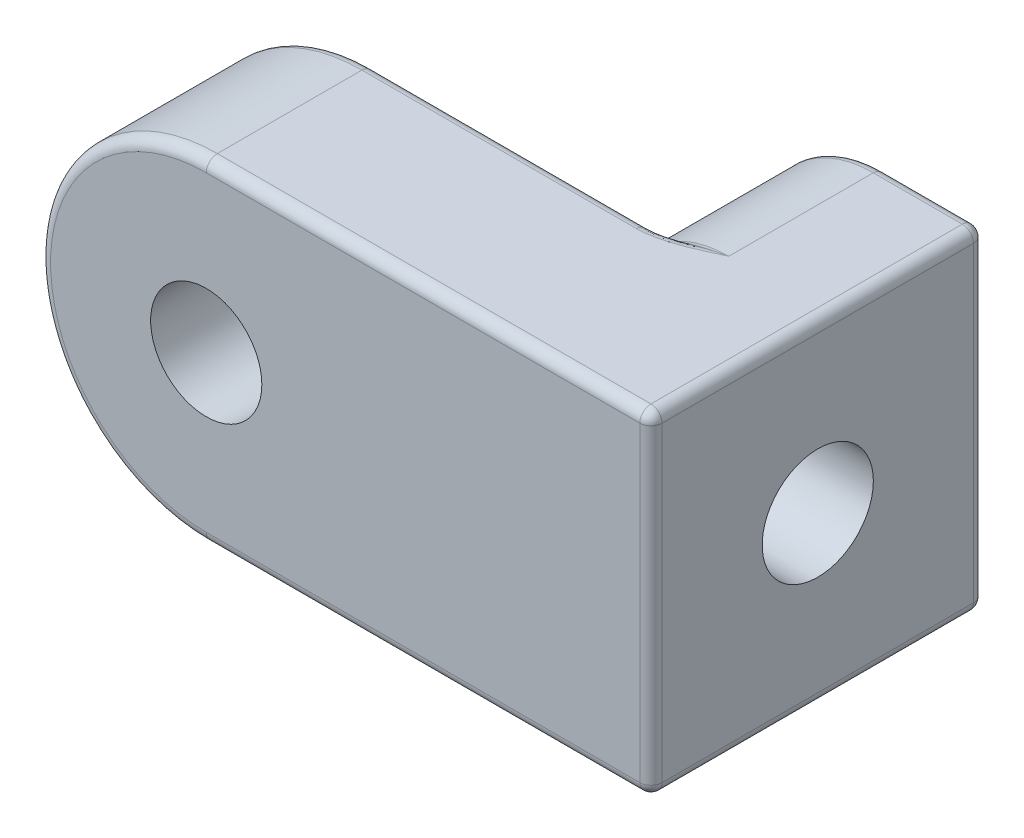
SolidWorks part; units mm, degrees
material "Malleable Cast Iron"
ref_plane "Front Plane" through (0, 0, 0) normal (0, 0, 1) x (1, 0, 0)
ref_plane "Top Plane" through (0, 0, 0) normal (0, 1, 0) x (1, 0, 0)
ref_plane "Right Plane" through (0, 0, 0) normal (1, 0, 0) x (0, 0, -1)
sketch "Sketch1" plane through (0, 0, 0) normal (0, 0, 1) x (1, 0, 0)
  line L0 (0, -30) -> (0, 30)
  line L1 (-80, -30) -> (0, -30)
  line L3 (-80, 30) -> (0, 30)
  arc A0 (-80, 30) -> (-80, -30) centre (-80, 0) ccw
  circle A2 centre (-80, 0) radius 10
  point P0 (0, 0)
  dimension "D1" = 20
  dimension "D2" = 80
  dimension "D3" = 30
extrude "Boss-Extrude1" add sketch "Sketch1" along normal blind 60
sketch "Sketch2" plane through (0, 0, 0) normal (0, 0, 1) x (1, 0, 0)
  line L1 (0, 30) -> (-80, 30) construction
  line L3 (-80, -30) -> (0, -30) construction
  line L8 (-70, 30) -> (-80, 30)
  line L9 (-70, -30) -> (-80, -30)
  line L11 (-70, -30) -> (-38, -30)
  line L13 (-70, 30) -> (-38, 30)
  line L14 (-38, -30) -> (-38, 30)
  arc A1 (-80, 30) -> (-80, -30) centre (-80, 0) ccw
  dimension "D1" = 42
extrude "Cut-Extrude2" cut sketch "Sketch2" along normal blind 30 contours L8 A1 L9 region at (-71.1229, 0, 0)
sketch "Sketch3" plane through (0, 0, 0) normal (1, 0, 0) x (0, 0, -1)
  circle A0 centre (-30, 0) radius 10
  dimension "D1" = 20
  dimension "D2" = 30
extrude "Cut-Extrude3" cut sketch "Sketch3" against normal blind 30
fillet "Fillet1" radius 20 2 edges at (-38, 30, 15) (-38, -30, 15)
fillet "Fillet2" radius 2 18 edges at (-40, 30, 60) (-40, -30, 60) (-32.1421, -24.1421, 30) (-32.1421, 24.1421, 30) (-49, 30, 30) (-110, 0, 30) (-32.1421, -24.1421, 0) (-9, -30, 0) (0, 0, 0) (-9, 30, 0) (-32.1421, 24.1421, 0) (-38, 0, 0) (0, -30, 30) (0, 30, 30) (0, 0, 60) (-110, 0, 60) (-38, 0, 30) (-49, -30, 30)
